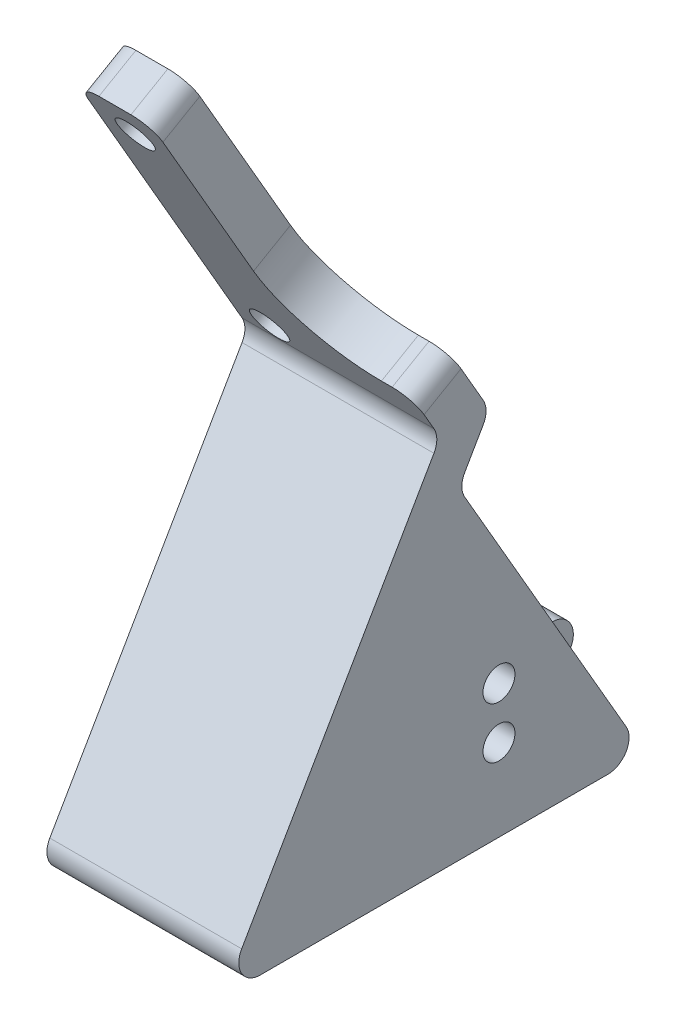
SolidWorks part; units mm, degrees
ref_plane "Plan de face" through (0, 0, 0) normal (0, 0, 1) x (1, 0, 0)
ref_plane "Plan de dessus" through (0, 0, 0) normal (0, 1, 0) x (1, 0, 0)
ref_plane "Plan de droite" through (0, 0, 0) normal (1, 0, 0) x (0, 0, -1)
sketch "Esquisse1" plane through (0, 0, 0) normal (1, 0, 0) x (0, 0, -1)
  line L1 (-37.5, 64.9519) -> (-40.9641, 62.9519)
  line L2 (-40.9641, 62.9519) -> (-24.9641, 35.2391)
  line L3 (-24.9641, 35.2391) -> (-45.3094, 0)
  line L4 (-45.3094, 0) -> (0, 0)
  line L5 (-38.3812, 4) -> (-12.7017, 4) construction
  line L6 (-12.7017, 4) -> (-25.5415, 26.2391) construction
  line L7 (-25.5415, 26.2391) -> (-38.3812, 4) construction
  line L8 (-12.7017, 4) -> (-12.7017, 0) construction
  line L9 (-37.5, 64.9519) -> (-20.3453, 35.2391)
  line L10 (-38.3812, 4) -> (-41.8453, 6) construction
  line L12 (-2.3094, 4) -> (0, 0)
  line L13 (-20.3453, 35.2391) -> (-23.2321, 30.2391)
  line L14 (-23.2321, 30.2391) -> (-8.0829, 4)
  line L15 (-8.0829, 4) -> (-2.3094, 4)
  line L16 (-25.5415, 26.2391) -> (-22.0774, 28.2391) construction
  dimension "D1" = 120
  dimension "D2" = 4
  dimension "D3" = 32
  dimension "D4" = 75
  dimension "D5" = 5
extrude "Boss.-Extru.1" add sketch "Esquisse1" along normal blind 18
sketch "Esquisse4" plane through (0, -2, 3.4641) normal (0, -0.5, 0.866) x (1, 0, 0)
  line L0 (0, 75) -> (0, 43) construction
  line L1 (18, 75) -> (7, 75)
  line L2 (18, 75) -> (18, 48)
  line L3 (18, 48) -> (7, 48)
  line L4 (7, 75) -> (7, 48)
  line L5 (18, 43) -> (0, 43) construction
  dimension "D1" = 7
  dimension "D2" = 5
extrude "Enlèv. mat.-Extru.1" cut sketch "Esquisse4" against normal up to next
sketch "Esquisse6" plane through (18, 0, 0) normal (1, 0, 0) x (0, 0, -1)
  line L0 (0, 0) -> (-2.3094, 4)
  line L1 (-2.3094, 4) -> (-8.0829, 4)
  line L8 (-45.3094, 0) -> (0, 0) construction
  line L9 (-5.7735, 0) -> (0, 0)
  line L10 (-8.0829, 4) -> (-5.7735, 0)
extrude "Enlèv. mat.-Extru.2" cut sketch "Esquisse6" against normal offset from surface (11 mm away) 7 up to face at (0, 26.2912, 22.523)
hole_wizard "Dégagement M31" positions "Esquisse2" profile "Esquisse3" hole size "M3" standard "ISO" end condition through all
sketch "Esquisse2" plane through (0, 0, 0) normal (0, 0.5, -0.866) x (-1, 0, 0)
  line L3 (-3.5, 46) -> (-3.5, 71.2) construction
  line L7 (-7, 75) -> (0, 75) construction
  line L8 (0, 40.6906) -> (0, 75) construction
  point P0 (-3.5, 71.2)
  point P2 (-3.5, 46)
  dimension "D1" = 25.2
  dimension "D2" = 3.8
  dimension "D3" = 3.5
sketch "Esquisse3" plane through (3.5, 61.661, 35.6) normal (1, 0, 0) x (0, 0.866, 0.5)
  line L0 (0, 0) -> (0, 39.2391)
  line L1 (0, 39.2391) -> (1.7, 39.2391)
  line L2 (1.7, 39.2391) -> (1.7, 0)
  line L5 (1.7, 0) -> (0, 0)
  line L11 (0, -6.35) -> (0, 107.95) construction
  dimension "Diamètre du perçage jusqu'au prochain" = 3.4
  dimension "Profondeur du perçage jusqu'au prochain" = 39.2391
sketch "Esquisse9" plane through (0, 0, 0) normal (-1, 0, 0) x (0, 0, 1)
  line L0 (19.4415, 15.2) -> (20.4415, 16.2)
  line L1 (20.4415, 16.2) -> (30.6415, 16.2)
  line L2 (19.4415, 15.2) -> (19.4415, 13.4)
  line L3 (20.4415, 4) -> (30.6415, 4)
  line L4 (31.6415, 15.2) -> (31.6415, 13.4)
  line L5 (19.4415, 16.2) -> (31.6415, 4) construction
  line L6 (19.4415, 4) -> (31.6415, 16.2) construction
  line L7 (30.6415, 16.2) -> (31.6415, 15.2)
  line L8 (30.6415, 4) -> (31.6415, 5)
  line L9 (19.4415, 5) -> (20.4415, 4)
  line L10 (19.4415, 11.6) -> (19.4415, 8.6)
  line L11 (31.6415, 11.6) -> (31.6415, 8.6)
  line L12 (31.6415, 6.8) -> (31.6415, 5)
  line L13 (19.4415, 6.8) -> (19.4415, 5)
  line L17 (25.5415, 4) -> (25.5415, 10.1) construction
  line L18 (38.3812, 4) -> (12.7017, 4) construction
  arc A0 (19.4415, 13.4) -> (19.4415, 11.6) centre (19.4415, 12.5) ccw
  arc A1 (19.4415, 8.6) -> (19.4415, 6.8) centre (19.4415, 7.7) ccw
  arc A2 (31.6415, 11.6) -> (31.6415, 13.4) centre (31.6415, 12.5) ccw
  arc A3 (31.6415, 6.8) -> (31.6415, 8.6) centre (31.6415, 7.7) ccw
  point P0 (25.5415, 10.1)
  dimension "D3" = 1.8
  dimension "D1" = 12.2
  dimension "D2" = 12.2
  dimension "D4" = 3.7
  dimension "D9" = 3.7
extrude "Enlèv. mat.-Extru.3" cut sketch "Esquisse9" against normal blind 8.4
sketch "Esquisse10" plane through (8.4, 0, 0) normal (-1, 0, 0) x (0, 0, 1)
  circle A0 centre (19.4415, 12.5) radius 0.9
  circle A1 centre (19.4415, 7.7) radius 0.9
  circle A2 centre (31.6415, 12.5) radius 0.9
  circle A3 centre (31.6415, 7.7) radius 0.9
extrude "Enlèv. mat.-Extru.4" cut sketch "Esquisse10" against normal blind 4
sketch "Esquisse11" plane through (0, 0, 0) normal (-1, 0, 0) x (0, 0, 1)
  line L0 (25.5415, 26.2391) -> (12.7017, 4)
  line L1 (12.7017, 4) -> (38.3812, 4)
  line L2 (38.3812, 4) -> (25.5415, 26.2391)
extrude "Enlèv. mat.-Extru.5" cut sketch "Esquisse11" against normal blind 5
fillet "Congé1" radius 2 14 edges at (9, 35.2391, 24.9641) (9, 0, 45.3094) (0, 63.9519, 39.2321) (9, 35.2391, 20.3453) (9, 30.2391, 23.2321) (3.5, 4, 8.0829) (3.5, 4, 2.3094) (3.5, 0, 0) (18, 40.5692, 25.7321) (12.5, 0, 5.7735) (2.5, 4, 38.3812) (2.5, 26.2391, 25.5415) (2.5, 4, 12.7017) (7, 63.9519, 39.2321)
fillet "Congé2" radius 8 1 edges at (7, 40.5692, 25.7321)
sketch "Esquisse13" plane through (8.4, 0, 0) normal (-1, 0, 0) x (0, 0, 1)
  circle A0 centre (19.4415, 12.5) radius 1.5
  circle A1 centre (19.4415, 7.7) radius 1.5
  dimension "D1" = 3
extrude "Enlèv. mat.-Extru.6" cut sketch "Esquisse13" against normal through all from offset 1.6 offset against normal yes
